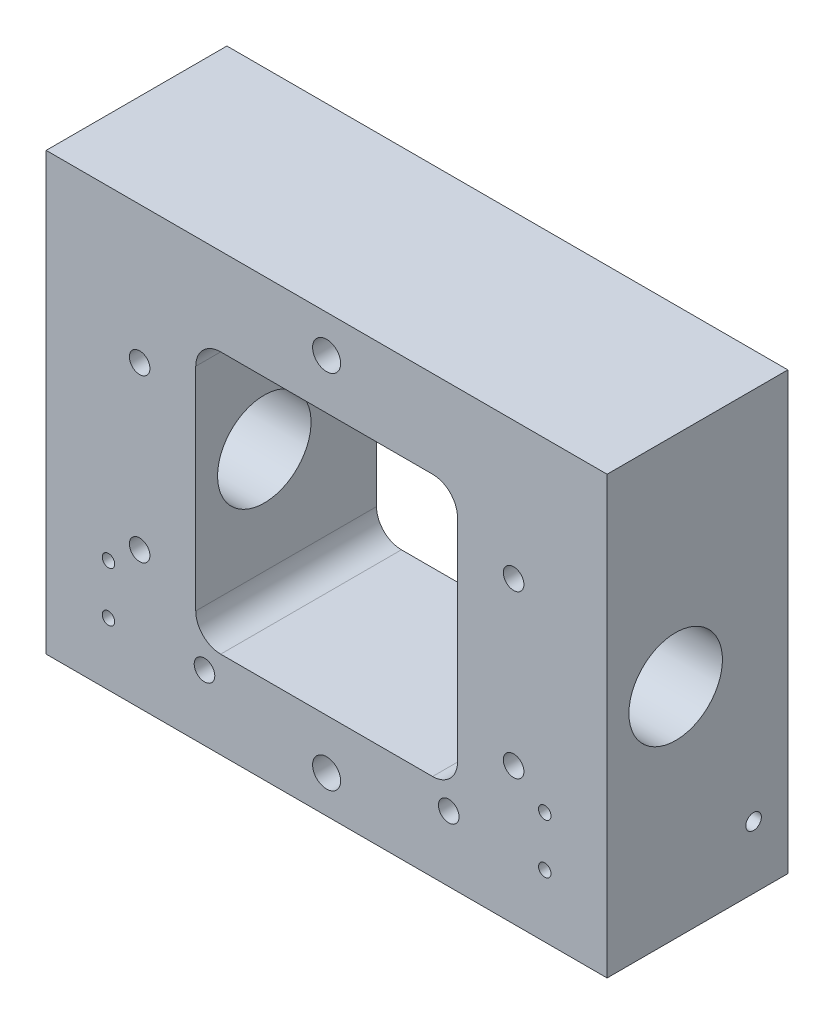
SolidWorks part; units mm, degrees
material "Lega 6061"
ref_plane "Piano frontale" through (0, 0, 0) normal (0, 0, 1) x (1, 0, 0)
ref_plane "Piano superiore" through (0, 0, 0) normal (0, 1, 0) x (1, 0, 0)
ref_plane "Piano destro" through (0, 0, 0) normal (1, 0, 0) x (0, 0, -1)
sketch "Schizzo1" plane through (0, 0, 0) normal (0, 0, 1) x (1, 0, 0)
  line L1 (0, 0) -> (90, 0)
  line L2 (0, 0) -> (0, 70)
  line L3 (0, 70) -> (90, 70)
  line L4 (90, 0) -> (90, 70)
  dimension "D1" = 90
  dimension "D2" = 70
extrude "Estrusione-Estrusione1" add sketch "Schizzo1" against normal blind 29
sketch "Schizzo2" plane through (0, 0, 0) normal (-1, 0, 0) x (0, 0, 1)
  line L0 (-29, 35) -> (0, 35) construction
  line L1 (-29, 70) -> (-29, 0) construction
  line L2 (0, 70) -> (0, 0) construction
  circle A0 centre (-11, 35) radius 7.5
  dimension "D1" = 15
  dimension "D2" = 18
extrude "Taglio-Estrusione1" cut sketch "Schizzo2" against normal through all
sketch "Schizzo3" plane through (0, 0, -29) normal (0, 0, -1) x (-1, 0, 0)
  line L0 (-94.314, 64) -> (4.9562, 64) construction
  line L2 (-90, 70) -> (0, 70) construction
  line L4 (-90, 35) -> (0, 35) construction
  line L5 (-90, 0) -> (-90, 70) construction
  line L6 (0, 70) -> (0, 0) construction
  line L7 (-94.314, 6) -> (4.9562, 6) construction
  line L8 (-45, 70) -> (-45, 0) construction
  line L9 (0, 0) -> (-90, 0) construction
  point P16 (-45, 64)
  point P17 (-45, 6)
  dimension "D1" = 6
hole_wizard "Foro lamato per Vite M4 a testa cilindrica piana-1" positions "Schizzo3D1" profile "Schizzo4" counterbore size "M4" standard "ISO" end condition through all
sketch3d "Schizzo3D1"
  point P0 (45, 64, -29)
  point P3 (45, 6, -29)
sketch "Schizzo4" plane through (45, 64, -29) normal (1, 0, 0) x (0, 1, 0)
  line L0 (0, 0) -> (0, 29)
  line L1 (0, 29) -> (2.25, 29)
  line L3 (2.25, 29) -> (2.25, 2.6)
  line L4 (2.25, 2.6) -> (4, 2.6)
  line L5 (4, 2.6) -> (4, 0)
  line L7 (4, 0) -> (0, 0)
  line L11 (0, -6.35) -> (0, 107.95) construction
  dimension "Thru Hole Dia." = 4.5
  dimension "Thru Hole Depth" = 29
  dimension "C'Bore Dia." = 8
  dimension "C'Bore Depth" = 2.6
ref_axis "Assi1" through (90, 35, -11) along (-1, 0, 0)
sketch "Schizzo14" plane through (0, 0, 0) normal (0, 0, 1) x (1, 0, 0)
  line L0 (45, 70) -> (45, 0) construction
  line L2 (62, 14) -> (28, 14)
  line L3 (66, 18) -> (66, 52)
  line L4 (90, 35) -> (0, 35) construction
  line L5 (62, 56) -> (28, 56)
  line L6 (24, 18) -> (24, 52)
  line L7 (66, 14) -> (24, 56) construction
  line L8 (66, 56) -> (24, 14) construction
  line L9 (0, 0) -> (90, 0) construction
  arc A0 (62, 56) -> (66, 52) centre (62, 52) cw
  arc A1 (66, 18) -> (62, 14) centre (62, 18) cw
  arc A2 (28, 14) -> (24, 18) centre (28, 18) cw
  arc A3 (24, 52) -> (28, 56) centre (28, 52) cw
  point P2 (45, 35)
  point P3 (45, 35)
  dimension "D1" = 4
  dimension "D2" = 42
  dimension "D3" = 42
  dimension "D4" = 14
extrude "Taglio-Estrusione4" cut sketch "Schizzo14" against normal through all
sketch "Schizzo16" plane through (0, 0, 0) normal (0, 0, 1) x (1, 0, 0)
  line L0 (45, 70) -> (45, 0) construction
  line L1 (0, 35) -> (90, 35) construction
  line L2 (0, 70) -> (0, 0) construction
  line L3 (0, 0) -> (90, 0) construction
  circle A0 centre (10, 10) radius 1
  circle A1 centre (80, 10) radius 1
  dimension "D1" = 2
  dimension "D2" = 10
  dimension "D3" = 10
  dimension "D4" = 35
  dimension "D5" = 25
extrude "Taglio-Estrusione6" cut sketch "Schizzo16" against normal through all
sketch "Schizzo17" plane through (0, 0, -29) normal (0, 0, -1) x (-1, 0, 0)
  line L0 (-45, 70) -> (-45, 0.5122) construction
  line L1 (-90, 70) -> (0, 70) construction
  line L2 (-45, 70) -> (-45, 0) construction
  line L3 (0, 35) -> (-90, 35) construction
  circle A0 centre (-10, 10) radius 8
  circle A1 centre (-80, 10) radius 8
  dimension "D1" = 16
extrude "Taglio-Estrusione8" cut sketch "Schizzo17" against normal blind 13
sketch "Schizzo18" plane through (0, 0, 0) normal (0, 0, 1) x (1, 0, 0)
  line L0 (0, 70) -> (90, 0) construction
  line L1 (90, 70) -> (0, 0) construction
  line L2 (45, 35) -> (45, 70) construction
  line L3 (15, 35.0996) -> (15, 74.2174) construction
  line L4 (24, 35) -> (0, 35) construction
  line L5 (24, 52) -> (24, 18) construction
  line L6 (90, 35) -> (0, 35) construction
  line L7 (90, 70) -> (0, 70) construction
  line L8 (45, 70) -> (45, 0) construction
  point P9 (15, 22)
  point P11 (45, 35)
  point P17 (15, 48)
  point P24 (75, 22)
  point P25 (75, 48)
  dimension "D1" = 13
  dimension "D2" = 30
hole_wizard "Foro filettato M4-1" positions "Schizzo20" profile "Schizzo19" tap size "M4" standard "ISO" end condition through all
sketch "Schizzo20" plane through (0, 0, 0) normal (0, 0, 1) x (1, 0, 0)
  point P0 (15, 48)
  point P3 (15, 22)
  point P6 (75, 48)
  point P9 (75, 22)
cosmetic thread "Filettatura del foro1" parameters "D2"=4
cosmetic thread "Filettatura del foro2" parameters "D2"=4
cosmetic thread "Filettatura del foro3" parameters "D2"=4
cosmetic thread "Filettatura del foro4" parameters "D2"=4
sketch "Schizzo19" plane through (15, 48, 0) normal (1, 0, 0) x (0, -1, 0)
  line L0 (0, 0) -> (0, 29)
  line L1 (0, 29) -> (1.65, 29)
  line L2 (1.65, 29) -> (1.65, 0)
  line L5 (1.65, 0) -> (0, 0)
  line L11 (0, -6.35) -> (0, 107.95) construction
  dimension "Thru Tap Drill Dia." = 3.3
  dimension "Thru Tap Drill Depth" = 29
sketch "Schizzo21" plane through (0, 0, -29) normal (0, 0, -1) x (-1, 0, 0)
  line L0 (-70, 73.919) -> (-70, -6.106) construction
  line L1 (-45, 70) -> (-45, 0) construction
  line L2 (-90, 70) -> (0, 0) construction
  line L3 (0, 70) -> (-90, 0) construction
  line L5 (-20, 72.5272) -> (-20, -6.106) construction
  point P6 (-70, 54.4444)
  point P9 (-70, 15.5556)
  point P14 (-20, 54.4444)
  point P15 (-20, 15.5556)
  dimension "D1" = 25
  dimension "D2" = 25
hole_wizard "Foro filettato M3-1" positions "Schizzo23" profile "Schizzo22" tap size "M3" standard "ISO"
sketch "Schizzo23" plane through (0, 0, -29) normal (0, 0, -1) x (-1, 0, 0)
  point P0 (-70, 54.4444)
  point P3 (-70, 15.5556)
  point P6 (-20, 54.4444)
  point P9 (-20, 15.5556)
sketch "Schizzo22" plane through (70, 54.4444, -29) normal (1, 0, 0) x (0, 1, 0)
  line L0 (0, 0) -> (0, 12.7511)
  line L1 (0, 12.7511) -> (1.25, 12)
  line L2 (1.25, 12) -> (1.25, 0)
  line L5 (1.25, 0) -> (0, 0)
  line L10 (0, 12.7511) -> (-1.25, 12) construction
  line L11 (0, -6.35) -> (0, 107.95) construction
  dimension "Tap Drill Dia." = 2.5
  dimension "Tap Drill Depth" = 12
  dimension "Drill Angle" = 118
cosmetic thread "Filettatura del foro5" parameters "D1"=8, "D2"=3
cosmetic thread "Filettatura del foro6" parameters "D1"=8, "D2"=3
cosmetic thread "Filettatura del foro7" parameters "D1"=8, "D2"=3
cosmetic thread "Filettatura del foro8" parameters "D1"=8, "D2"=3
sketch "Schizzo24" plane through (0, 0, 0) normal (-1, 0, 0) x (0, 0, 1)
  line L0 (-16, 18) -> (-16, 2) construction
  line L1 (-16, 10) -> (-29, 10) construction
  point P6 (-23.5, 10)
  dimension "D1" = 7.5
hole_wizard "Foro filettato M3-2" positions "Schizzo26" profile "Schizzo27" tap size "M3" standard "ISO" end condition up to next
sketch "Schizzo26" plane through (0, 0, 0) normal (-1, 0, 0) x (0, 0, 1)
  point P0 (-23.5, 10)
sketch "Schizzo27" plane through (0, 10, -23.5) normal (0, 1, 0) x (0, 0, 1)
  line L0 (0, 0) -> (0, 2)
  line L1 (0, 2) -> (1.25, 2)
  line L2 (1.25, 2) -> (1.25, 0)
  line L5 (1.25, 0) -> (0, 0)
  line L11 (0, -6.35) -> (0, 107.95) construction
  dimension "Thru Tap Drill Dia." = 2.5
  dimension "Thru Tap Drill Depth" = 2
cosmetic thread "Filettatura del foro9" parameters "D2"=3
sketch "Schizzo28" plane through (0, 0, 0) normal (0, -1, 0) x (1, 0, 0)
  line L0 (2, -16) -> (18, -16) construction
  line L1 (10, -16) -> (10, -29) construction
  line L2 (94.314, -29) -> (-4.9562, -29) construction
  point P8 (10, -23.5)
  dimension "D1" = 7.5
hole_wizard "Foro filettato M3-3" positions "Schizzo30" profile "Schizzo31" tap size "M3" standard "ISO" end condition up to next
sketch "Schizzo30" plane through (0, 0, 0) normal (0, -1, 0) x (-1, 0, 0)
  point P0 (-10, 23.5)
sketch "Schizzo31" plane through (10, 0, -23.5) normal (1, 0, 0) x (0, 0, -1)
  line L0 (0, 0) -> (0, 2)
  line L1 (0, 2) -> (1.25, 2)
  line L2 (1.25, 2) -> (1.25, 0)
  line L5 (1.25, 0) -> (0, 0)
  line L11 (0, -6.35) -> (0, 107.95) construction
  dimension "Thru Tap Drill Dia." = 2.5
  dimension "Thru Tap Drill Depth" = 2
cosmetic thread "Filettatura del foro10" parameters "D2"=3
sketch "Schizzo32" plane through (0, 0, 0) normal (0, -1, 0) x (1, 0, 0)
  line L0 (72, -16) -> (88, -16) construction
  line L1 (72, -16) -> (88, -16) construction
  line L2 (80, -16) -> (80, -29) construction
  line L3 (94.314, -29) -> (-4.9562, -29) construction
  line L5 (90, -29) -> (90, 0) construction
  point P9 (80, -23.5)
  dimension "D1" = 7.5
  dimension "D2" = 5.5
  dimension "D3" = 10
hole_wizard "Foro filettato M3-4" positions "Schizzo34" profile "Schizzo35" tap size "M3" standard "ISO" end condition up to next
sketch "Schizzo34" plane through (0, 0, 0) normal (0, -1, 0) x (-1, 0, 0)
  point P0 (-80, 23.5)
sketch "Schizzo35" plane through (80, 0, -23.5) normal (1, 0, 0) x (0, 0, -1)
  line L0 (0, 0) -> (0, 2)
  line L1 (0, 2) -> (1.25, 2)
  line L2 (1.25, 2) -> (1.25, 0)
  line L5 (1.25, 0) -> (0, 0)
  line L11 (0, -6.35) -> (0, 107.95) construction
  dimension "Thru Tap Drill Dia." = 2.5
  dimension "Thru Tap Drill Depth" = 2
cosmetic thread "Filettatura del foro11" parameters "D2"=3
sketch "Schizzo36" plane through (90, 0, 0) normal (1, 0, 0) x (0, 0, -1)
  line L0 (16, 18) -> (16, 2) construction
  line L1 (16, 10) -> (29, 10) construction
  point P8 (23.5, 10)
hole_wizard "Foro filettato M3-5" positions "Schizzo38" profile "Schizzo37" tap size "M3" standard "ISO" end condition up to next
sketch "Schizzo38" plane through (90, 0, 0) normal (1, 0, 0) x (0, 0, -1)
  point P0 (23.5, 10)
cosmetic thread "Filettatura del foro12" parameters "D2"=3
sketch "Schizzo37" plane through (90, 10, -23.5) normal (0, 1, 0) x (0, 0, -1)
  line L0 (0, 0) -> (0, 2)
  line L1 (0, 2) -> (1.25, 2)
  line L2 (1.25, 2) -> (1.25, 0)
  line L5 (1.25, 0) -> (0, 0)
  line L11 (0, -6.35) -> (0, 107.95) construction
  dimension "Thru Tap Drill Dia." = 2.5
  dimension "Thru Tap Drill Depth" = 2
sketch "Schizzo39" plane through (0, 0, 0) normal (0, 0, 1) x (1, 0, 0)
  line L0 (45, 0) -> (45, 37.4704) construction
  point P0 (64.5937, 10.5)
  point P3 (25.4063, 10.5)
hole_wizard "Foro filettato M4-2" positions "Schizzo41" profile "Schizzo40" tap size "M4" standard "ISO"
sketch "Schizzo41" plane through (0, 0, 0) normal (0, 0, 1) x (1, 0, 0)
  point P0 (64.5937, 10.5)
  point P3 (25.4063, 10.5)
sketch "Schizzo40" plane through (64.5937, 10.5, 0) normal (1, 0, 0) x (0, -1, 0)
  line L0 (0, 0) -> (0, 11.0914)
  line L1 (0, 11.0914) -> (1.65, 10.1)
  line L2 (1.65, 10.1) -> (1.65, 0)
  line L5 (1.65, 0) -> (0, 0)
  line L10 (0, 11.0914) -> (-1.65, 10.1) construction
  line L11 (0, -6.35) -> (0, 107.95) construction
  dimension "Tap Drill Dia." = 3.3
  dimension "Tap Drill Depth" = 10.1
  dimension "Drill Angle" = 118
cosmetic thread "Filettatura del foro13" parameters "D1"=8, "D2"=4
cosmetic thread "Filettatura del foro14" parameters "D1"=8, "D2"=4
sketch "Schizzo42" plane through (0, 0, 0) normal (0, 0, 1) x (1, 0, 0)
  line L0 (10, 10) -> (10, 19.2804) construction
  line L1 (45, 6) -> (45, 35) construction
  line L2 (45, 70) -> (45, 0) construction
  circle A0 centre (10, 18) radius 1
  circle A1 centre (80, 18) radius 1
  dimension "D1" = 2
  dimension "D2" = 8
extrude "Taglio-Estrusione9" cut sketch "Schizzo42" against normal blind 12
